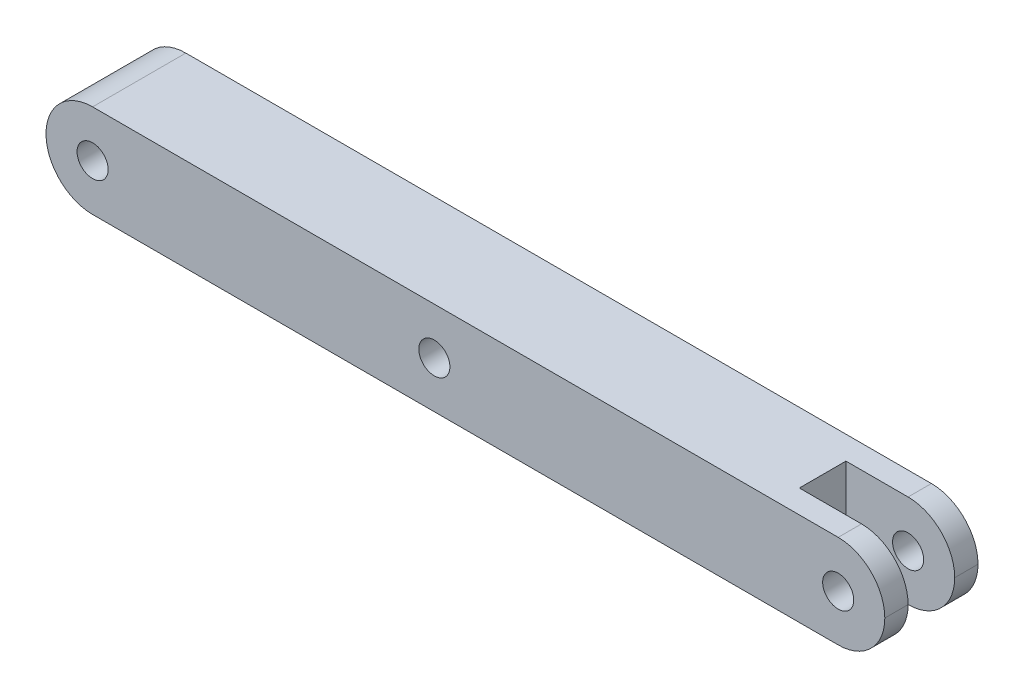
SolidWorks part; units mm, degrees
material "6061 Alloy"
ref_plane "Front Plane" through (0, 0, 0) normal (0, 0, 1) x (1, 0, 0)
ref_plane "Top Plane" through (0, 0, 0) normal (0, 1, 0) x (1, 0, 0)
ref_plane "Right Plane" through (0, 0, 0) normal (1, 0, 0) x (0, 0, -1)
sketch "Sketch1" plane through (0, 0, 0) normal (0, 0, 1) x (1, 0, 0)
  line L0 (0, 0) -> (0, 30)
  line L1 (0, 30) -> (270, 30)
  line L2 (270, 30) -> (270, 0)
  line L3 (270, 0) -> (0, 0)
  dimension "D1" = 30
  dimension "D2" = 270
extrude "Boss-Extrude1" add sketch "Sketch1" along normal mid plane 30
sketch "Sketch2" plane through (0, 30, 0) normal (0, 1, 0) x (1, 0, 0)
  line L20 (270, 7.5) -> (235, 7.5)
  line L21 (270, -15) -> (270, 15) construction
  line L22 (235, 7.5) -> (235, -7.5)
  line L23 (235, -7.5) -> (270, -7.5)
  line L25 (270, 7.5) -> (270, -7.5)
  point P6 (0, 0)
  dimension "D3" = 15
  dimension "D4" = 35
extrude "Cut-Extrude1" cut sketch "Sketch2" against normal up to next
sketch "Sketch3" plane through (0, 0, 15) normal (0, 0, 1) x (1, 0, 0)
  line L0 (0, 15) -> (15, 15) construction
  line L1 (0, 30) -> (0, 0) construction
  line L2 (255, 15) -> (270, 15) construction
  line L3 (270, 0) -> (270, 30) construction
  circle A0 centre (15, 15) radius 5
  circle A1 centre (255, 15) radius 5
  circle A2 centre (125, 15) radius 5
  dimension "D1" = 10
  dimension "D2" = 10
  dimension "D6" = 10
  dimension "D3" = 15
  dimension "D4" = 15
  dimension "D5" = 130
extrude "Cut-Extrude2" cut sketch "Sketch3" against normal through all both and the other way through all
fillet "Fillet3" radius 15 6 edges at (270, 0, -11.25) (270, 30, -11.25) (270, 0, 11.25) (270, 30, 11.25) (0, 0, 0) (0, 30, 0)
